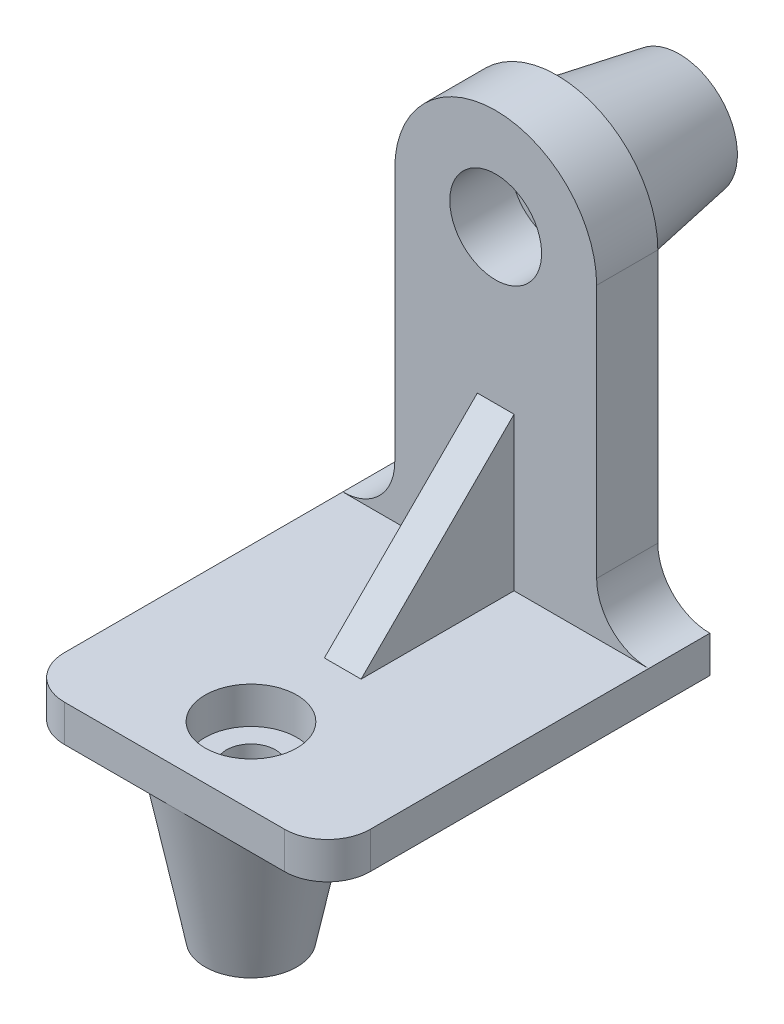
SolidWorks part; units mm, degrees
ref_plane "Alzado" through (0, 0, 0) normal (0, 0, 1) x (1, 0, 0)
ref_plane "Planta" through (0, 0, 0) normal (0, 1, 0) x (1, 0, 0)
ref_plane "Vista lateral" through (0, 0, 0) normal (1, 0, 0) x (0, 0, -1)
sketch "Croquis1" plane through (0, 0, 0) normal (0, 1, 0) x (1, 0, 0)
  line L1 (50, 62.5) -> (-50, 62.5)
  line L2 (50, 62.5) -> (50, -62.5)
  line L3 (50, -62.5) -> (-50, -62.5)
  line L4 (-50, 62.5) -> (-50, -62.5)
  line L5 (50, 62.5) -> (-50, -62.5) construction
  line L6 (50, -62.5) -> (-50, 62.5) construction
  circle A0 centre (0, -37.5) radius 15
  point P0 (0, 0)
  dimension "D3" = 30
  dimension "D4" = 25
  dimension "D1" = 100
  dimension "D2" = 125
extrude "Saliente-Extruir1" add sketch "Croquis1" along normal blind 12
fillet "Redondeo1" radius 14 1 edges at (50, 6, 62.5)
fillet "Redondeo2" radius 14 1 edges at (-50, 6, 62.5)
sketch "Croquis2" plane through (0, 12, 0) normal (0, 1, 0) x (1, 0, 0)
  line L0 (-50, 42.5) -> (50, 42.5) construction
  line L1 (-6, 42.5) -> (-6, -7.5)
  line L2 (-6, -7.5) -> (6, -7.5)
  line L3 (6, -7.5) -> (6, 42.5)
  line L4 (-50, 62.5) -> (-50, -48.5)
  line L5 (-36, -62.5) -> (36, -62.5)
  line L6 (50, -48.5) -> (50, 62.5)
  line L7 (50, 62.5) -> (-50, 62.5)
  line L8 (-50, 62.5) -> (-50, 42.5)
  line L10 (50, 42.5) -> (50, 62.5)
  line L11 (50, 62.5) -> (-50, 62.5)
  line L12 (-6, 42.5) -> (6, 42.5)
  arc A2 (-50, -48.5) -> (-36, -62.5) centre (-36, -48.5) ccw
  arc A3 (36, -62.5) -> (50, -48.5) centre (36, -48.5) ccw
  point P12 (0, -7.5)
  dimension "D4" = 12
  dimension "D2" = 20
  dimension "D3" = 50
  dimension "D1" = 0
extrude "Saliente-Extruir2" add sketch "Croquis2" along normal blind 50 contours L12 L1 L2 L3 region at (0, 12, -17.5)
chamfer "Chaflán1" distance 50 angle 45 1 edges at (0, 62, 7.5)
sketch "Croquis3" plane through (0, 0, -42.5) normal (0, 0, -1) x (-1, 0, 0)
  line L2 (50, 12) -> (-50, 12) construction
  line L3 (-50, 12) -> (-50, 0) construction
  line L4 (-6, 12) -> (6, 12) construction
  line L10 (50, 12) -> (-50, 12)
  line L11 (-50, 12) -> (-50, 0)
  line L12 (-6, 12) -> (6, 12)
  line L16 (-33, 29) -> (-33, 112)
  line L17 (33, 112) -> (33, 29)
  arc A0 (-50, 12) -> (-33, 29) centre (-50, 29) ccw
  arc A1 (-33, 112) -> (33, 112) centre (0, 112) cw
  arc A2 (50, 12) -> (33, 29) centre (50, 29) cw
  circle A3 centre (0, 112) radius 15
  line M5 (-6, 12) -> (6, 12)
  line M6 (6, 12) -> (6, 62)
  line M7 (6, 62) -> (-6, 62)
  line M8 (-6, 62) -> (-6, 12)
  dimension "D1" = 17
  dimension "D2" = 17
  dimension "D3" = 33
  dimension "D5" = 30
  dimension "D4" = 100
extrude "Saliente-Extruir6" add sketch "Croquis3" along normal blind 20 contours L10 A2 L17 A1 L16 A0 A3 M8 M7 M6 | M8 M5 M6 M7 region at (0, 73.7027, -42.5) region at (0, 37, -42.5)
sketch "Croquis4" plane through (0, 0, -62.5) normal (0, 0, -1) x (-1, 0, 0)
  line L5 (-50, 0) -> (50, 0)
  line L6 (50, 0) -> (50, 12)
  line L7 (33, 29) -> (33, 112)
  line L8 (-33, 112) -> (-33, 29)
  line L9 (-50, 12) -> (-50, 0)
  circle A0 centre (0, 112) radius 26
  arc A3 (33, 29) -> (50, 12) centre (50, 29) ccw
  arc A4 (33, 112) -> (-33, 112) centre (0, 112) ccw
  arc A5 (-50, 12) -> (-33, 29) centre (-50, 29) ccw
  arc A7 (33, 112) -> (-33, 112) centre (0, 112) ccw
  circle M18 centre (0, 112) radius 15
  dimension "D2" = 52
  dimension "D1" = 0
extrude "Saliente-Extruir7" add sketch "Croquis4" along normal blind 40 draft 9.926 contours M18 | A0 M18 region at (25.2646, 112, -62.5) region at (0, 112, -62.5)
sketch "Croquis7" plane through (0, 0, -102.5) normal (0, 0, -1) x (-1, 0, 0)
  circle A0 centre (0, 112) radius 10
  point P1 (0, 0)
  dimension "D2" = 20
extrude "Cortar-Extruir1" cut sketch "Croquis7" against normal up to next
sketch "Croquis8" plane through (0, 0, 0) normal (0, -1, 0) x (1, 0, 0)
  circle A2 centre (0, 37.5) radius 25
  point P1 (0, 0)
  dimension "D1" = 50
extrude "Saliente-Extruir8" add sketch "Croquis8" along normal blind 50 draft 11.31
sketch "Croquis11" plane through (0, -50, 0) normal (0, -1, 0) x (1, 0, 0)
  circle A0 centre (0, 37.5) radius 8
  circle A1 centre (0, 37.5) radius 15
  circle A2 centre (0, 37.5) radius 15
  dimension "D2" = 16
  dimension "D1" = 0
extrude "Cortar-Extruir2" cut sketch "Croquis11" against normal up to next contours A0
